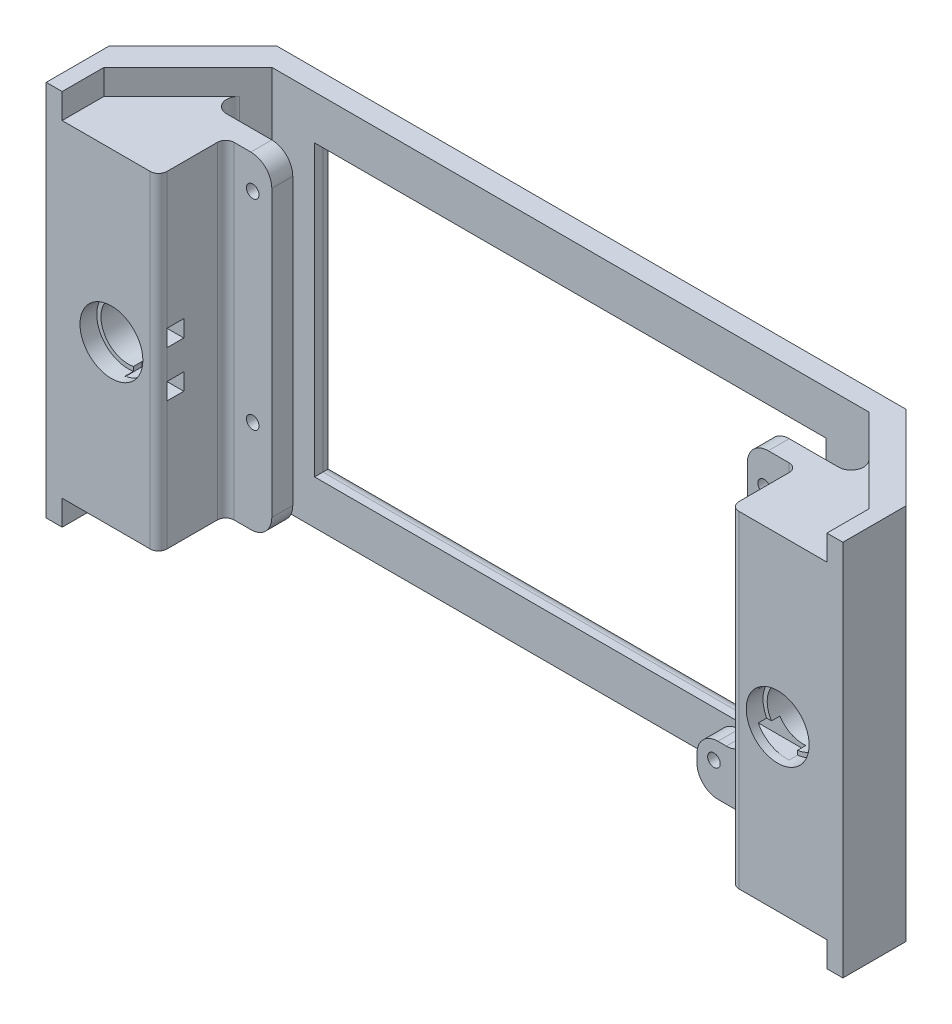
SolidWorks part; units mm, degrees
ref_plane "Front Plane" through (0, 0, 0) normal (0, 0, 1) x (1, 0, 0)
ref_plane "Top Plane" through (0, 0, 0) normal (0, 1, 0) x (1, 0, 0)
ref_plane "Right Plane" through (0, 0, 0) normal (1, 0, 0) x (0, 0, -1)
sketch "Sketch1" plane through (0, 0, 0) normal (0, 0, 1) x (1, 0, 0)
  line L1 (-95, 45) -> (95, 45)
  line L2 (-95, 45) -> (-95, -45)
  line L3 (-95, -45) -> (95, -45)
  line L4 (95, 45) -> (95, -45)
  line L5 (-95, 45) -> (95, -45) construction
  line L6 (-95, -45) -> (95, 45) construction
  line L7 (-61, 34.5) -> (61, 34.5)
  line L8 (-61, 34.5) -> (-61, -34.5)
  line L9 (-61, -34.5) -> (61, -34.5)
  line L10 (61, 34.5) -> (61, -34.5)
  line L11 (-61, 34.5) -> (61, -34.5) construction
  line L12 (-61, -34.5) -> (61, 34.5) construction
  point P0 (0, 0)
  point P6 (0, 0)
  dimension "D1" = 122
  dimension "D2" = 190
  dimension "D3" = 69
  dimension "D4" = 90
extrude "Boss-Extrude1" add sketch "Sketch1" along normal blind 5
sketch "Sketch2" plane through (0, 0, 5) normal (0, 0, 1) x (1, 0, 0)
  line L0 (-95, -45) -> (95, -45) construction
  line L1 (-95, 45) -> (-91.2, 45)
  line L2 (-95, 45) -> (-95, -45)
  line L3 (-95, -45) -> (-91.2, -45)
  line L4 (-91.2, 45) -> (-91.2, -45)
  line L5 (0, 0) -> (0, 45) construction
  line L6 (95, 45) -> (-95, 45) construction
  line L7 (95, -45) -> (91.2, -45)
  line L8 (91.2, 45) -> (91.2, -45)
  line L9 (95, 45) -> (91.2, 45)
  line L10 (95, 45) -> (95, -45)
  dimension "D1" = 3.8
extrude "Boss-Extrude2" add sketch "Sketch2" along normal blind 30
sketch "Sketch3" plane through (0, 45, 0) normal (0, 1, 0) x (1, 0, 0)
  line L0 (-91.2, -35) -> (-91.2, -5) construction
  line L1 (-91.2, -14) -> (-57.2, -14)
  line L2 (-91.2, -14) -> (-91.2, -19)
  line L3 (-91.2, -19) -> (-57.2, -19)
  line L4 (-57.2, -14) -> (-57.2, -19)
  line L5 (91.2, -35) -> (91.2, -5) construction
  line L6 (91.2, -14) -> (44.2, -14)
  line L7 (91.2, -14) -> (91.2, -19)
  line L8 (91.2, -19) -> (44.2, -19)
  line L9 (44.2, -14) -> (44.2, -19)
  line L10 (91.2, -5) -> (-91.2, -5) construction
  dimension "D1" = 9
  dimension "D2" = 9
  dimension "D3" = 5
  dimension "D4" = 5
  dimension "D5" = 34
  dimension "D6" = 47
extrude "Boss-Extrude3" add sketch "Sketch3" against normal up to surface (90 mm away) up to face at (0, -45, 18.75)
sketch "Sketch4" plane through (0, 0, 19) normal (0, 0, 1) x (1, 0, 0)
  line L0 (91.2, -45) -> (91.2, 45) construction
  line L1 (-91.2, 45) -> (91.2, 45)
  line L2 (-91.2, 45) -> (-91.2, 39)
  line L3 (-91.2, 39) -> (91.2, 39)
  line L4 (91.2, 45) -> (91.2, 39)
  line L5 (0, 0) -> (-91.2, 0) construction
  line L6 (-91.2, -45) -> (-91.2, 45) construction
  line L7 (-91.2, -39) -> (91.2, -39)
  line L8 (91.2, -45) -> (91.2, -39)
  line L9 (-91.2, -45) -> (91.2, -45)
  line L10 (-91.2, -45) -> (-91.2, -39)
  dimension "D1" = 6
extrude "Cut-Extrude1" cut sketch "Sketch4" against normal blind 5
sketch "Sketch5" plane through (0, 0, 19) normal (0, 0, 1) x (1, 0, 0)
  line L0 (0, 0) -> (-61.75, 0) construction
  line L1 (-70.2, 37.38) -> (70.2, 37.38) construction
  line L2 (-70.2, 37.38) -> (-70.2, -37.38) construction
  line L3 (-70.2, -37.38) -> (70.2, -37.38) construction
  line L4 (70.2, 37.38) -> (70.2, -37.38) construction
  line L5 (-70.2, 37.38) -> (70.2, -37.38) construction
  line L6 (-70.2, -37.38) -> (70.2, 37.38) construction
  line L7 (-61.75, 0) -> (-61.75, 31.13) construction
  line L8 (-61.75, 0) -> (-61.75, -16.61) construction
  line L9 (48.25, 0) -> (60.23, 0) construction
  line L10 (60.23, 0) -> (60.23, 31.13) construction
  line L11 (0, 0) -> (48.25, 0) construction
  line L12 (48.25, 0) -> (48.25, -31.38) construction
  circle A0 centre (-61.75, 31.13) radius 1.5
  circle A1 centre (-61.75, -16.61) radius 1.5
  circle A2 centre (60.23, 31.13) radius 1.5
  circle A3 centre (48.25, -31.38) radius 1.5
  point P0 (0, 0)
  dimension "D10" = 3
  dimension "D11" = 3
  dimension "D12" = 3
  dimension "D13" = 3
  dimension "D1" = 140.4
  dimension "D2" = 74.76
  dimension "D3" = 61.75
  dimension "D4" = 31.13
  dimension "D5" = 16.61
  dimension "D6" = 60.23
  dimension "D7" = 31.13
  dimension "D8" = 48.25
  dimension "D9" = 31.38
extrude "Cut-Extrude2" cut sketch "Sketch5" against normal up to surface (5 mm away) up to face at (67.7, 0, 14)
sketch "Sketch6" plane through (0, 0, 19) normal (0, 0, 1) x (1, 0, 0)
  line L1 (44.2, 39) -> (56.2, 39)
  line L2 (44.2, 39) -> (44.2, -27)
  line L3 (44.2, -27) -> (56.2, -27)
  line L4 (56.2, 39) -> (56.2, -27)
  dimension "D1" = 12
  dimension "D2" = 66
extrude "Cut-Extrude3" cut sketch "Sketch6" against normal up to surface (5 mm away) up to face at (46.75, -31.38, 14)
fillet "Fillet3" radius 3 4 edges at (-61, 0, 0) (0, -34.5, 0) (61, 0, 0) (0, 34.5, 0)
chamfer "Chamfer6" distance 20 angle 45 4 edges at (91.2, 0, 5) (95, 0, 0) (-95, 0, 0) (-91.2, 0, 5)
sketch "Sketch7" plane through (0, 39, 0) normal (0, 1, 0) x (1, 0, 0)
  line L0 (-85.2, -19) -> (-91.2, -25)
  line L1 (-91.2, -25) -> (-91.2, -35)
  line L2 (-91.2, -35) -> (-68.2, -35)
  line L3 (-68.2, -35) -> (-68.2, -19)
  line L4 (-85.2, -19) -> (-57.2, -19) construction
  line L5 (-68.2, -19) -> (-85.2, -19)
  line L6 (0, 0) -> (0, -5) construction
  line L7 (71.2, -5) -> (-71.2, -5) construction
  line L8 (68.2, -35) -> (68.2, -19)
  line L9 (91.2, -35) -> (68.2, -35)
  line L10 (91.2, -25) -> (91.2, -35)
  line L11 (85.2, -19) -> (91.2, -25)
  line L12 (68.2, -19) -> (85.2, -19)
  dimension "D1" = 23
extrude "Boss-Extrude4" add sketch "Sketch7" against normal up to surface (78 mm away) up to face at (-69.95, -39, 16.5)
fillet "Fillet4" radius 5 6 edges at (-57.2, -39, 16.5) (-57.2, 39, 16.5) (56.2, 39, 16.5) (44.2, -39, 16.5) (44.2, -27, 16.5) (56.2, -27, 16.5)
fillet "Fillet5" radius 2 4 edges at (-68.2, 0, 35) (68.2, 0, 35) (68.2, 0, 19) (-68.2, 0, 19)
fillet "Fillet6" radius 3 2 edges at (-80.2, 0, 14) (80.2, 0, 14)
sketch "Sketch9" plane through (0, 0, 35) normal (0, 0, 1) x (1, 0, 0)
  line L6 (0, 0) -> (0, -45) construction
  line L7 (-71.2, -45) -> (71.2, -45) construction
  line L8 (-95, 45) -> (-95, -45) construction
  line L9 (-95, 39) -> (-79.45, 39) construction
  line L10 (-95, 39) -> (-95, -0.9074) construction
  line L11 (-95, -0.9074) -> (-79.45, -0.9074) construction
  line L12 (-79.45, 39) -> (-79.45, -0.9074) construction
  line L13 (-91.2, 39) -> (-70.2, 39) construction
  circle A0 centre (-79.45, -0.9074) radius 6.5
  circle A1 centre (79.45, -0.9074) radius 6.5
  dimension "D3" = 13
  dimension "D1" = 39.9074
  dimension "D2" = 15.55
extrude "Cut-Extrude4" cut sketch "Sketch9" against normal blind 10
sketch "Sketch10" plane through (0, 0, 35) normal (0, 0, 1) x (1, 0, 0)
  circle A0 centre (-79.45, -0.9074) radius 7.5
  circle A1 centre (79.45, -0.9074) radius 7.5
  dimension "D1" = 15
  dimension "D2" = 15
extrude "Cut-Extrude5" cut sketch "Sketch10" against normal blind 4
sketch "Sketch12" plane through (-68.2, 0, 0) normal (1, 0, 0) x (0, 0, -1)
  line L0 (-33, -4.4074) -> (-29, -4.4074)
  line L1 (-33, 39) -> (-23, 39) construction
  line L2 (-33, 39) -> (-33, -0.9074) construction
  line L3 (-33, -0.9074) -> (-23, -0.9074) construction
  line L4 (-23, 39) -> (-23, -0.9074) construction
  line L5 (-33, 6.5926) -> (-23, 6.5926) construction
  line L6 (-33, 6.5926) -> (-33, -8.4074) construction
  line L7 (-33, -8.4074) -> (-23, -8.4074) construction
  line L8 (-23, 6.5926) -> (-23, -8.4074) construction
  line L9 (-33, 6.5926) -> (-23, -8.4074) construction
  line L10 (-33, -8.4074) -> (-23, 6.5926) construction
  line L11 (-33, 6.5926) -> (-29, 6.5926)
  line L12 (-33, 6.5926) -> (-33, 2.5926)
  line L13 (-33, 2.5926) -> (-29, 2.5926)
  line L14 (-29, 6.5926) -> (-29, 2.5926)
  line L15 (-29, -8.4074) -> (-29, -4.4074)
  line L16 (-33, -8.4074) -> (-29, -8.4074)
  line L17 (-33, -8.4074) -> (-33, -4.4074)
  point P5 (-28, -0.9074)
  dimension "D1" = 39.9074
  dimension "D2" = 10
  dimension "D3" = 15
  dimension "D4" = 10
  dimension "D5" = 4
  dimension "D6" = 4
extrude "Cut-Extrude6" cut sketch "Sketch12" against normal blind 10 and the other way blind 148.4
